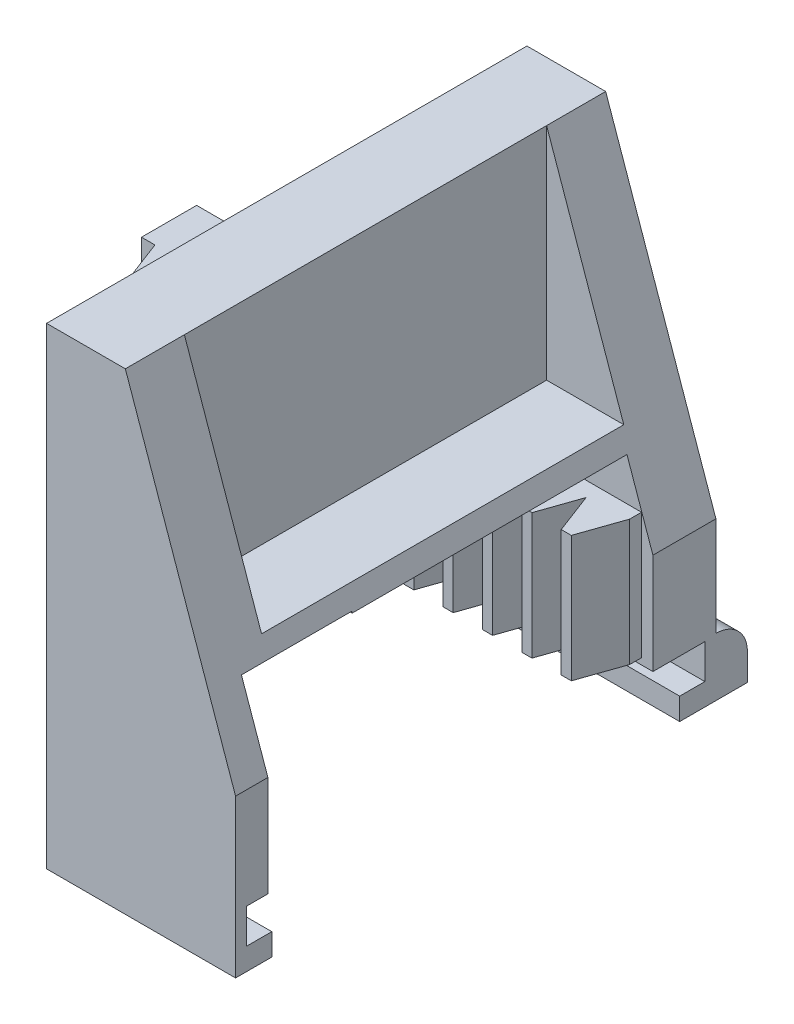
SolidWorks part; units mm, degrees
ref_plane "Front Plane" through (0, 0, 0) normal (0, 0, 1) x (1, 0, 0)
ref_plane "Top Plane" through (0, 0, 0) normal (0, 1, 0) x (1, 0, 0)
ref_plane "Right Plane" through (0, 0, 0) normal (1, 0, 0) x (0, 0, -1)
sketch "Sketch1" plane through (0, 0, 0) normal (0, 0, 1) x (1, 0, 0)
  line L0 (0, 0) -> (0, -30)
  line L1 (0, -30) -> (12, -30)
  line L2 (12, -30) -> (12, -20)
  line L3 (12, -20) -> (5, 0)
  line L4 (5, 0) -> (0, 0)
  dimension "D1" = 30
  dimension "D2" = 12
  dimension "D3" = 10
  dimension "D4" = 5
extrude "Boss-Extrude1" add sketch "Sketch1" against normal blind 30.5
sketch "Sketch4" plane through (0, 0, 0) normal (-1, 0, 0) x (0, 0, 1)
  line L0 (-30.5, 0) -> (-30.5, -30) construction
  line L1 (-26.5, -15.288) -> (-6.5, -15.288)
  line L2 (-26.5, -15.288) -> (-26.5, -30.288)
  line L3 (-26.5, -30.288) -> (-6.5, -30.288)
  line L4 (-6.5, -15.288) -> (-6.5, -30.288)
  point P4 (-26.5, -22.788)
  dimension "D1" = 20
  dimension "D2" = 15
  dimension "D3" = 4
extrude "Cut-Extrude2" cut sketch "Sketch4" against normal blind 25 contours L2 L1 L4 L3
ref_plane "Plane1" through (0, 0, -15.25) normal (0, 0, 1) x (1, 0, 0)
sketch "Sketch6" plane through (0, 0, -15.25) normal (0, 0, 1) x (1, 0, 0)
  line L0 (5, 0) -> (5, -14)
  line L1 (5, -14) -> (9.9, -14)
  line L2 (12, -20) -> (5, 0) construction
  line L3 (9.9, -14) -> (5, 0)
  dimension "D1" = 14
extrude "Cut-Extrude4" cut sketch "Sketch6" against normal mid plane 23
ref_plane "Plane2" through (0, -26, 0) normal (0, 1, 0) x (1, 0, 0)
sketch "Sketch7" plane through (0, -26, 0) normal (0, 1, 0) x (1, 0, 0)
  line L0 (11.2768, 29.25) -> (-19.7232, 29.25)
  line L62 (-16.5, 15.25) -> (16.5, 15.25) construction
  line L162 (11.2768, 29.25) -> (11.2768, 25.75)
  line L172 (-19.7232, 25.75) -> (-19.7232, 29.25)
  line L243 (11.2768, 25.75) -> (-19.7232, 25.75)
  dimension "D2" = 31
  dimension "D3" = 3.5
  dimension "D7" = 14
sketch "Sketch8" plane through (0, 0, 0) normal (-1, 0, 0) x (0, 0, 1)
  line L0 (-9.0524, -15.2) -> (-2.0524, -15.2)
  line L2 (-6.5, -30) -> (0, -30) construction
  line L6 (-2.0524, -15.2) -> (-2.0524, -26.4)
  line L7 (-2.0524, -26.4) -> (-9.0524, -26.4)
  line L9 (-9.0524, -26.4) -> (-9.0524, -15.2)
  point P6 (-2.0524, -13)
  dimension "D1" = 7
  dimension "D2" = 11.2
  dimension "D3" = 3.6
extrude "Cut-Extrude5" cut sketch "Sketch8" against normal through all
sketch "Sketch9" plane through (0, 0, 0) normal (-1, 0, 0) x (0, 0, 1)
  line L0 (-6.5, -26.4) -> (-0.7, -26.4)
  line L1 (-6.5, -26.4) -> (-6.5, -30) construction
  line L2 (-0.7, -26.4) -> (-0.7, -28.6)
  line L3 (-0.7, -28.6) -> (-2.3, -28.6)
  line L4 (-2.3, -28.6) -> (-2.3, -30.2967)
  line L5 (-2.3, -30.2967) -> (-6.5, -30.2967)
  line L6 (-6.5, -30.2967) -> (-6.5, -26.4)
  line L7 (-6.5, -30) -> (0, -30) construction
  line L8 (-15.25, -16.5) -> (-15.25, 16.5) construction
  line L9 (-24, -30.2967) -> (-24, -26.4)
  line L10 (-28.2, -30.2967) -> (-24, -30.2967)
  line L11 (-28.2, -28.6) -> (-28.2, -30.2967)
  line L12 (-29.8, -28.6) -> (-28.2, -28.6)
  line L13 (-29.8, -26.4) -> (-29.8, -28.6)
  line L14 (-24, -26.4) -> (-29.8, -26.4)
  dimension "D1" = 5.8
  dimension "D2" = 2.2
  dimension "D3" = 1.4
  dimension "D4" = 1.6
extrude "Cut-Extrude6" cut sketch "Sketch9" against normal through all
extrude "Boss-Extrude3" add sketch "Sketch7" along normal blind 8
sketch "Sketch10" plane through (0, -18, 0) normal (0, 1, 0) x (1, 0, 0)
  line L0 (11.2768, 25.75) -> (10.3197, 22.9986)
  line L2 (10.3197, 22.9986) -> (9.6791, 22.9986)
  line L3 (9.6791, 22.9986) -> (8.6309, 25.75)
  line L4 (-19.7232, 25.75) -> (11.2768, 25.75) construction
  line L5 (8.6309, 25.75) -> (11.2768, 25.75)
  point P3 (8.6734, 25.75)
  point P4 (9.6791, 22.9986)
  point P5 (8.6309, 25.75)
extrude "Boss-Extrude4" add sketch "Sketch10" against normal up to vertex (8 mm away) up to point (-19.7232, -26, -25.75)
pattern_linear "LPattern1" count 12 spacing 2.5 along (-1, 0, 0) of "Boss-Extrude4"
sketch "Sketch11" plane through (0, 0, -30.5) normal (0, 0, -1) x (-1, 0, 0)
  line L0 (-12, -30) -> (-12, -20) construction
  line L1 (-12, -26.3) -> (0, -26.3)
  line L2 (-12, -26.3) -> (-12, -30)
  line L3 (-12, -30) -> (0, -30)
  line L4 (0, -26.3) -> (0, -30)
  dimension "D1" = 3.7
extrude "Boss-Extrude5" add sketch "Sketch11" along normal blind 2
fillet "Fillet1" radius 2 1 edges at (6, -26.3, -32.5)
